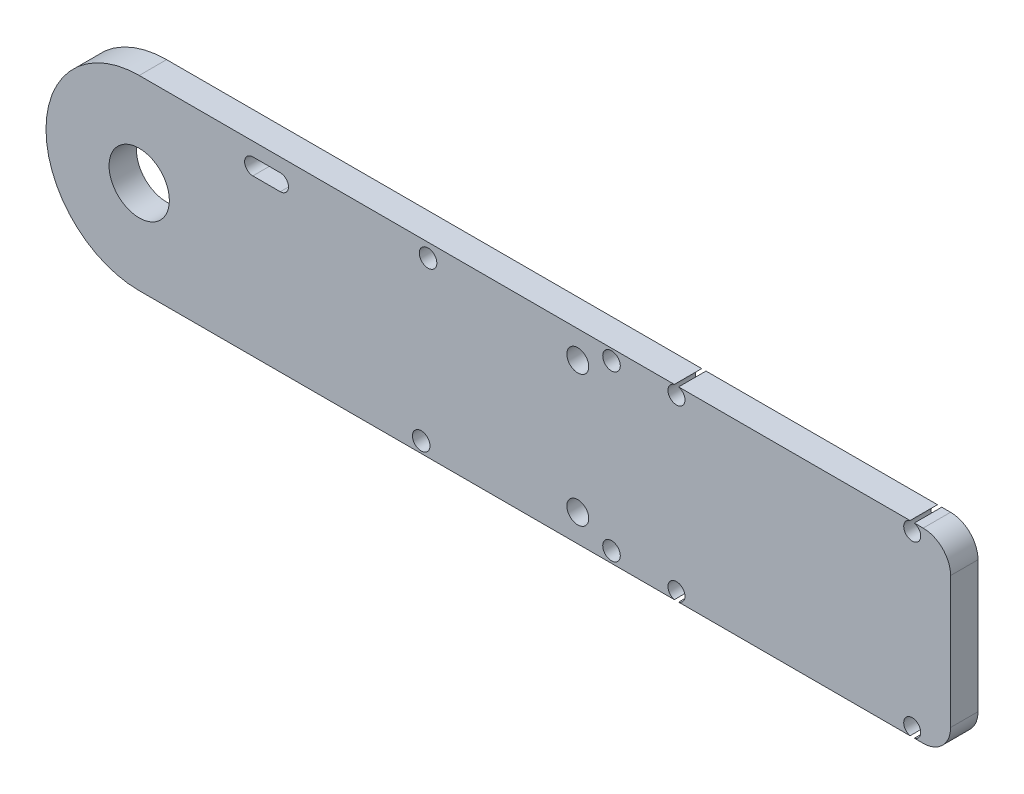
SolidWorks part; units mm, degrees
material "Acrylic (Medium-high impact)"
ref_plane "Front Plane" through (0, 0, 0) normal (0, 0, 1) x (1, 0, 0)
ref_plane "Top Plane" through (0, 0, 0) normal (0, 1, 0) x (1, 0, 0)
ref_plane "Right Plane" through (0, 0, 0) normal (1, 0, 0) x (0, 0, -1)
sketch "Sketch2" plane through (0, 0, 0) normal (0, 0, 1) x (1, 0, 0)
  line L0 (0, 17) -> (0, -17)
  line L1 (0, 17) -> (148, 17)
  line L2 (0, -17) -> (148, -17)
  line L3 (148, 17) -> (148, -17)
  line L4 (0, 0) -> (-17, 0)
  circle A0 centre (0, 0) radius 17
  circle A1 centre (0, 0) radius 5.5
  dimension "D1" = 34
  dimension "D3" = 11
  dimension "D2" = 165
extrude "Boss-Extrude1" add sketch "Sketch2" along normal mid plane 5 contours A1 L0 A0 | A0 L2 L3 L1 | A1 L4 A0 L0 | A1 L0 A0 L4 region at (7.7856, 0, 0) region at (80.6224, 0, 0) region at (-7.7856, 7.7856, 0) region at (-7.7856, -7.7856, 0)
fillet "Fillet1" radius 5 2 edges at (148, -17, 0) (148, 17, 0)
sketch "Sketch3" plane through (0, 0, -2.5) normal (0, 0, -1) x (-1, 0, 0)
  line L0 (-119.5, 17) -> (-119.5, -17)
  line L1 (-119.5, 0) -> (-98, 0)
  line L2 (-98, 0) -> (-98, 15.5)
  line L3 (-148, 12) -> (-148, -12)
  line L4 (-143, -17) -> (0, -17)
  line L5 (0, 17) -> (-143, 17)
  line L6 (-148, 12) -> (-148, -12)
  line L7 (-143, -17) -> (0, -17)
  line L8 (0, 17) -> (-143, 17)
  line L9 (-119.5, 0) -> (-80, 0)
  line L10 (-80, 0) -> (-80, 15)
  line L11 (-80, 15) -> (-86.149, 15)
  line L12 (0, 0) -> (0, 12)
  line L13 (0, 0) -> (-80, 0)
  line L14 (-25.7291, 13) -> (-20.7291, 13) construction
  line L17 (-25.7291, 14.5) -> (-20.7291, 14.5)
  line L18 (-25.7291, 11.5) -> (-20.7291, 11.5)
  line L19 (0, 0) -> (18.4819, 0)
  line L20 (-80, 0.6163) -> (-80, 6.1951)
  line L21 (-80, 0) -> (-80, 12)
  circle A0 centre (0, 0) radius 12
  circle A1 centre (-98, 15.5) radius 1.55
  circle A2 centre (-98, -15.5) radius 1.55
  arc A3 (-148, -12) -> (-143, -17) centre (-143, -12) ccw
  arc A4 (0, -17) -> (0, 17) centre (0, 0) ccw
  arc A5 (-143, 17) -> (-148, 12) centre (-143, 12) ccw
  arc A6 (-148, -12) -> (-143, -17) centre (-143, -12) ccw
  arc A7 (0, -17) -> (0, 17) centre (0, 0) ccw
  arc A8 (-143, 17) -> (-148, 12) centre (-143, 12) ccw
  circle A9 centre (-141, -15.5) radius 1.55
  circle A10 centre (-141, 15.5) radius 1.55
  circle A11 centre (-86.149, 15) radius 1.6
  circle A12 centre (-86.149, -15) radius 1.6
  circle A13 centre (-51.4387, -15) radius 1.6
  circle A14 centre (-52.6874, 14.5) radius 1.6
  circle A15 centre (0, 12) radius 2.1
  circle A16 centre (12, 0) radius 2.1
  circle A17 centre (-7.6279, -12) radius 2.1
  circle A18 centre (-12, 0) radius 2.1
  arc A21 (-25.7291, 14.5) -> (-25.7291, 11.5) centre (-25.7291, 13) ccw
  arc A22 (-20.7291, 11.5) -> (-20.7291, 14.5) centre (-20.7291, 13) ccw
  circle A23 centre (-80, 12) radius 2
  circle A25 centre (-80, -12) radius 2
  point P35 (-23.2291, 13)
  point P48 (12, 0)
  point P53 (-12, 0)
  point P54 (-7.6279, -12)
  point P56 (-78.2225, -15)
  point P59 (-83.7286, -15)
  point P60 (-90.9398, 15)
  point P61 (-86.149, 15)
  point P62 (-52.6874, 14.5)
  point P63 (-51.4387, -15)
  dimension "D2" = 24
  dimension "D6" = 3.1
  dimension "D10" = 3.2
  dimension "D11" = 4.2
  dimension "D13" = 80
  dimension "D18" = 4.2
  dimension "D12" = 4.2
  dimension "D19" = 4.2
  dimension "D21" = 4
  dimension "D3" = 21.5
  dimension "D4" = 15.5
  dimension "D5" = 98
  dimension "D7" = 27
  dimension "D8" = 15
  dimension "D14" = 5
  dimension "D15" = 3
  dimension "D16" = 4
  dimension "D20" = 12
  dimension "D1" = 0
extrude "Cut-Extrude1" cut sketch "Sketch3" against normal through all contours L18 A22 L17 A21 | L10 A23 L21 | L21 A23 L10 | A25 | A11 | A12 | A2 | A1 | A10 | A9 region at (98, 16.9565, -2.5) region at (141, 15.4947, -2.5) region at (87.7037, 15, -2.5) region at (80.8488, 12, -2.5) region at (79.1512, 12, -2.5) region at (141, -15.4947, -2.5) region at (98, -15.4947, -2.5) region at (23.2291, 13, -2.5) region at (86.149, -15, -2.5) region at (80, -12, -2.5)
extrude "Cut-Extrude2" cut sketch "Sketch3<4>" against normal blind 10 contours L18 A22 L17 A21 | A12 | A11 | A13 | A14 | A10 | A9 | A1 | A2 | L21 A23 L10 | L10 A23 L21 | A25 region at (98, 16.9565, -2.5) region at (141, 15.4947, -2.5) region at (87.7037, 15, -2.5) region at (80.8488, 12, -2.5) region at (79.1512, 12, -2.5) region at (141, -15.4947, -2.5) region at (98, -15.4947, -2.5) region at (23.2291, 13, -2.5) region at (86.149, -15, -2.5) region at (51.4387, -15, -2.5) region at (52.6874, 14.5, -2.5) region at (80, -12, -2.5)
sketch "Sketch3<4>" plane through (0, 0, -2.5) normal (0, 0, -1) x (-1, 0, 0) same geometry as "Sketch3"
sketch "Sketch4" plane through (0, 0, -2.5) normal (0, 0, -1) x (-1, 0, 0)
  circle A0 centre (-52.6874, 14.5) radius 2.5
  circle A1 centre (-51.4387, -15) radius 2.5
  dimension "D1" = 5
  dimension "D2" = 5
